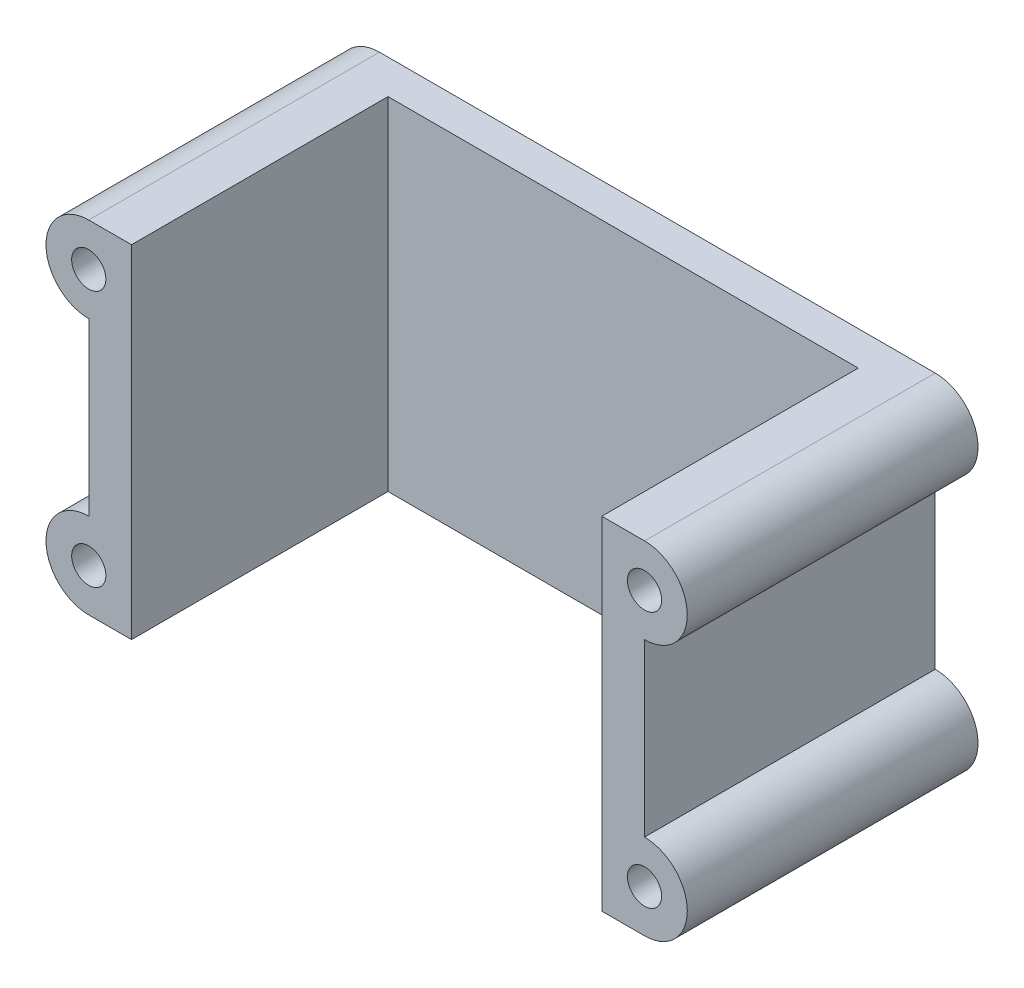
SolidWorks part; units mm, degrees
ref_plane "Front Plane" through (0, 0, 0) normal (0, 0, 1) x (1, 0, 0)
ref_plane "Top Plane" through (0, 0, 0) normal (0, 1, 0) x (1, 0, 0)
ref_plane "Right Plane" through (0, 0, 0) normal (1, 0, 0) x (0, 0, -1)
sketch "Sketch1" plane through (0, 0, 0) normal (0, 0, 1) x (1, 0, 0)
  line L1 (-32.5, 20) -> (32.5, 20)
  line L2 (-32.5, 20) -> (-32.5, -20)
  line L3 (-32.5, -20) -> (32.5, -20)
  line L4 (32.5, 20) -> (32.5, -20)
  line L5 (-32.5, 20) -> (32.5, -20) construction
  line L6 (-32.5, -20) -> (32.5, 20) construction
  point P0 (0, 0)
  dimension "D1" = 65
  dimension "D2" = 40
extrude "Boss-Extrude1" add sketch "Sketch1" along normal blind 4
sketch "Sketch2" plane through (0, 0, 4) normal (0, 0, 1) x (1, 0, 0)
  line L0 (-32.5, -20) -> (32.5, -20) construction
  line L1 (-32.5, 20) -> (-27.5, 20)
  line L2 (-32.5, 20) -> (-32.5, -20)
  line L3 (-32.5, -20) -> (-27.5, -20)
  line L4 (-27.5, 20) -> (-27.5, -20)
  line L6 (32.5, 20) -> (27.5, 20)
  line L7 (32.5, 20) -> (32.5, -20)
  line L8 (32.5, -20) -> (27.5, -20)
  line L9 (27.5, 20) -> (27.5, -20)
  dimension "D1" = 5
  dimension "D2" = 5
extrude "Boss-Extrude2" add sketch "Sketch2" along normal blind 30
sketch "Sketch3" plane through (0, 0, 0) normal (0, 0, 1) x (1, 0, 0)
  line L0 (-32.5, 20) -> (-32.5, -20) construction
  line L1 (-27.5, 20) -> (-32.5, 20) construction
  line L2 (-32.5, 20) -> (-32.5, 10)
  arc A0 (-32.5, 20) -> (-32.5, 10) centre (-32.5, 15) ccw
  dimension "D1" = 10
extrude "Boss-Extrude3" add sketch "Sketch3" along normal blind 34
sketch "Sketch5" plane through (0, 0, 34) normal (0, 0, 1) x (1, 0, 0)
  circle A0 centre (-32.5, 15) radius 2
  dimension "D1" = 4
extrude "Cut-Extrude1" cut sketch "Sketch5" against normal blind 34
mirror "Mirror1" about plane through (0, 0, 0) normal (1, 0, 0) of "Cut-Extrude1", "Boss-Extrude3" second plane through (0, 0, 0) second plane normal (0, 1, 0)
